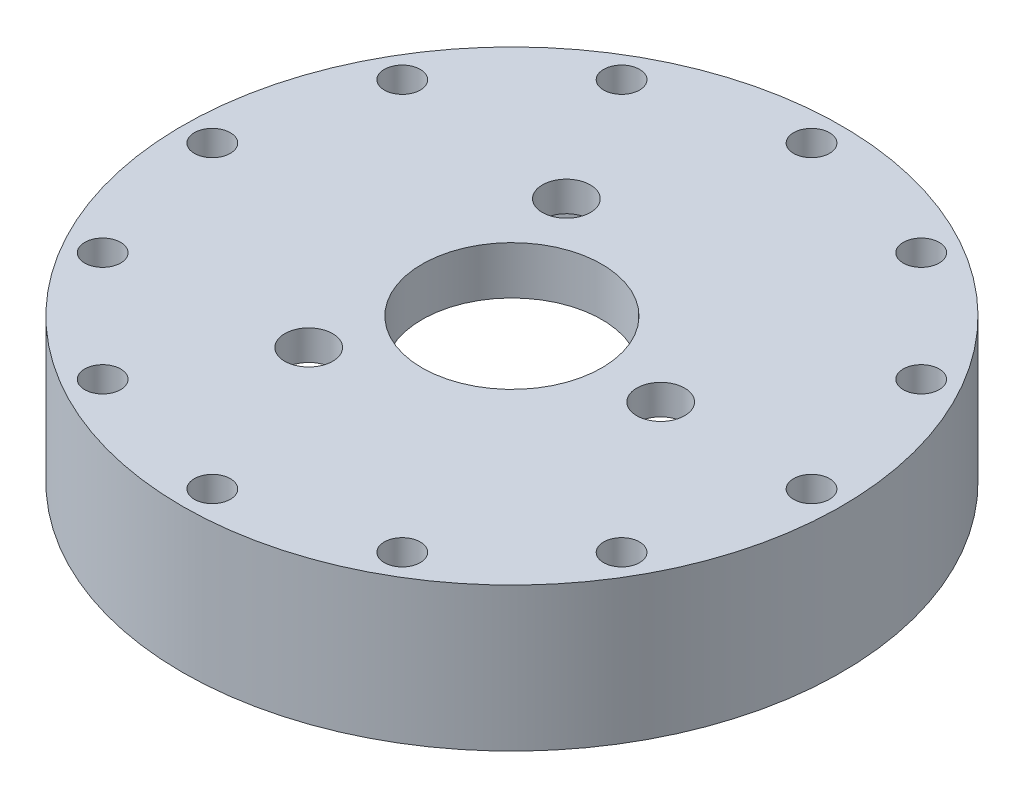
SolidWorks part; units mm, degrees
ref_plane "Front Plane" through (0, 0, 0) normal (0, 0, 1) x (1, 0, 0)
ref_plane "Top Plane" through (0, 0, 0) normal (0, 1, 0) x (1, 0, 0)
ref_plane "Right Plane" through (0, 0, 0) normal (1, 0, 0) x (0, 0, -1)
sketch "Sketch1" plane through (0, 0, 0) normal (0, 1, 0) x (1, 0, 0)
  line L0 (0, 22.5) -> (0, 0) construction
  line L1 (0, 0) -> (12.1644, 18.9282) construction
  line L2 (0, 0) -> (-12.1644, 18.9282) construction
  line L3 (-20.4667, 9.3468) -> (0, 0) construction
  line L4 (0, 0) -> (-22.271, -3.2021) construction
  circle A0 centre (0, 0) radius 22.5
  circle A1 centre (0, 0) radius 27.5
  circle A2 centre (0, 22.5) radius 4
  circle A3 centre (12.1644, 18.9282) radius 4
  circle A4 centre (20.4667, 9.3468) radius 4
  circle A5 centre (22.271, -3.2021) radius 4
  circle A6 centre (17.0044, -14.7344) radius 4
  circle A7 centre (6.339, -21.5886) radius 4
  circle A8 centre (-6.339, -21.5886) radius 4
  circle A9 centre (-17.0044, -14.7344) radius 4
  circle A10 centre (-22.271, -3.2021) radius 4
  circle A11 centre (-20.4667, 9.3468) radius 4
  circle A12 centre (-12.1644, 18.9282) radius 4
  point P27 (0, 0)
  dimension "D1" = 45
  dimension "D2" = 55
  dimension "D3" = 8
  dimension "D4" = 11
extrude "Boss-Extrude2" add sketch "Sketch1" along normal blind 8 contours A1 A12 A0 A2 A3 A4 A5 A6 A7 A8 A9 A10 A11 | A0 A11 | A0 A11 | A0 A12 | A0 A12 | A0 A2 | A0 A2 | A0 A3 | A0 A3 | A0 A4 | A0 A4 | A0 A5 | A0 A5 | A0 A6 | A0 A6 | A0 A7 | A0 A7 | A0 A8 | A0 A8 | A0 A9 | A0 A9 | A0 A10 | A0 A10 | A12 region at (20.5288, 0, 2.9516) region at (23.8864, 0, 3.4343) region at (18.8657, 0, -8.6157) region at (21.9512, 0, -10.0248) region at (18.2378, 0, 15.8031) region at (15.6742, 0, 13.5818) region at (11.2128, 0, -17.4475) region at (13.0467, 0, -20.3011) region at (6.7988, 0, 23.1545) region at (5.8431, 0, 19.8998) region at (0, 0, -20.7399) region at (0, 0, -24.132) region at (-6.7988, 0, 23.1545) region at (-5.8431, 0, 19.8998) region at (-11.2128, 0, -17.4475) region at (-13.0467, 0, -20.3011) region at (-18.2378, 0, 15.8031) region at (-15.6742, 0, 13.5818) region at (-18.8657, 0, -8.6157) region at (-21.9512, 0, -10.0248) region at (-23.8864, 0, 3.4343) region at (-20.5288, 0, 2.9516) region at (-26.7222, 0, 0)
sketch "Sketch2" plane through (0, 8, 0) normal (0, 1, 0) x (1, 0, 0)
  line L1 (12.413, 0) -> (-6.2065, 10.75) construction
  line L2 (-6.2065, 10.75) -> (-6.2065, -10.75) construction
  line L3 (-6.2065, -10.75) -> (12.413, 0) construction
  circle A0 centre (0, 0) radius 27.5
  circle A1 centre (0, 0) radius 7.5
  circle A2 centre (0, 0) radius 6.2065 construction
  circle A3 centre (-6.2065, 10.75) radius 2
  circle A4 centre (12.413, 0) radius 2
  circle A5 centre (-6.2065, -10.75) radius 2
  point P16 (0, 0)
  dimension "D1" = 15
  dimension "D2" = 55
  dimension "D4" = 4
  dimension "D3" = 21.5
  dimension "D5" = 3
extrude "Boss-Extrude3" add sketch "Sketch2" along normal blind 4
fillet "Fillet2" radius 1 22 edges at (19.3447, 4, 11.4905) (10.0616, 4, 20.125) (2.416, 4, 22.3699) (14.1266, 4, 17.5126) (-2.416, 4, 22.3699) (-10.0616, 4, 20.125) (-14.1266, 4, 17.5126) (-19.3447, 4, 11.4905) (-21.352, 4, 7.0951) (-22.4861, 4, -0.7921) (-21.7984, 4, -5.575) (-18.4882, 4, -12.8233) (-15.3239, 4, -16.4751) (-8.6205, 4, -20.7831) (-3.9842, 4, -22.1444) (3.9842, 4, -22.1444) (8.6205, 4, -20.7831) (15.3239, 4, -16.4751) (18.4882, 4, -12.8233) (21.7984, 4, -5.575) (22.4861, 4, -0.7921) (21.352, 4, 7.0951)
sketch "Sketch8" plane through (0, 0, 0) normal (0, -1, 0) x (1, 0, 0)
  circle A0 centre (0, 0) radius 25 construction
  circle A1 centre (0, -25) radius 1.5
  circle A2 centre (-12.5, -21.6506) radius 1.5
  circle A3 centre (-21.6506, -12.5) radius 1.5
  circle A4 centre (-25, 0) radius 1.5
  circle A5 centre (-21.6506, 12.5) radius 1.5
  circle A6 centre (-12.5, 21.6506) radius 1.5
  circle A7 centre (0, 25) radius 1.5
  circle A8 centre (12.5, 21.6506) radius 1.5
  circle A9 centre (21.6506, 12.5) radius 1.5
  circle A10 centre (25, 0) radius 1.5
  circle A11 centre (21.6506, -12.5) radius 1.5
  circle A12 centre (12.5, -21.6506) radius 1.5
  point P30 (0, 0)
  dimension "D1" = 50
  dimension "D2" = 3
  dimension "D3" = 12
extrude "Cut-Extrude1" cut sketch "Sketch8" against normal through all
sketch "Sketch9" plane through (0, 8, 0) normal (0, -1, 0) x (1, 0, 0)
  circle A0 centre (0, 0) radius 12.413 construction
  circle A1 centre (12.413, 0) radius 4.25
  circle A2 centre (-6.2065, -10.75) radius 4.25
  circle A3 centre (-6.2065, 10.75) radius 4.25
  point P13 (0, 0)
  dimension "D1" = 8.5
  dimension "D2" = 3
extrude "Cut-Extrude2" cut sketch "Sketch9" against normal blind 1.5
